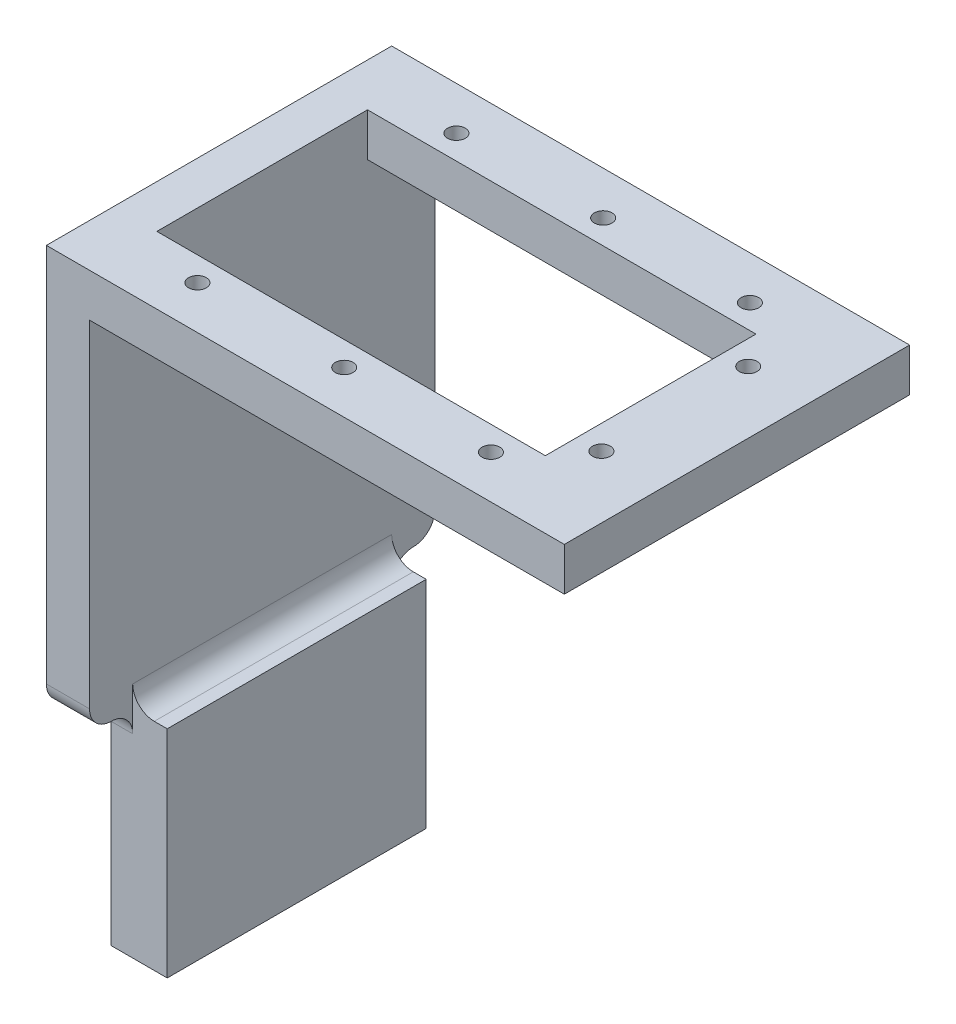
SolidWorks part; units mm, degrees
material "ABS"
ref_plane "Front Plane" through (0, 0, 0) normal (0, 0, 1) x (1, 0, 0)
ref_plane "Top Plane" through (0, 0, 0) normal (0, 1, 0) x (1, 0, 0)
ref_plane "Right Plane" through (0, 0, 0) normal (1, 0, 0) x (0, 0, -1)
sketch "Sketch1" plane through (0, 0, 0) normal (0, 1, 0) x (1, 0, 0)
  line L1 (0, 0) -> (60, 0)
  line L2 (0, 0) -> (0, 40)
  line L3 (0, 40) -> (60, 40)
  line L4 (60, 0) -> (60, 40)
  line L5 (5, 7.8) -> (50, 7.8)
  line L6 (5, 7.8) -> (5, 32.2)
  line L7 (5, 32.2) -> (50, 32.2)
  line L8 (50, 7.8) -> (50, 32.2)
  point P9 (5, 20)
  point P10 (0, 20)
  dimension "D1" = 40
  dimension "D2" = 60
  dimension "D3" = 45
  dimension "D4" = 24.4
  dimension "D5" = 5
extrude "Boss-Extrude1" add sketch "Sketch1" along normal blind 5
sketch "Sketch6" plane through (0, 0, 0) normal (0, -1, 0) x (1, 0, 0)
  line L0 (0, -40) -> (0, 0) construction
  line L1 (0, -40) -> (5, -40)
  line L2 (0, -40) -> (0, 0)
  line L3 (0, 0) -> (5, 0)
  line L4 (5, -40) -> (5, 0)
  line L5 (0, 0) -> (60, 0) construction
  line L6 (5, -32.2) -> (5, -7.8) construction
  line L7 (60, -40) -> (0, -40) construction
extrude "Boss-Extrude4" add sketch "Sketch6" along normal blind 41.5
sketch "Sketch7" plane through (0, -41.5, 0) normal (0, -1, 0) x (-1, 0, 0)
  line L0 (-5, 0) -> (0, 0) construction
  line L1 (-2.5, 35) -> (-9, 35)
  line L2 (-2.5, 35) -> (-2.5, 5)
  line L3 (-2.5, 5) -> (-9, 5)
  line L4 (-9, 35) -> (-9, 5)
  line L5 (-5, 40) -> (-5, 0) construction
  line L6 (-2.5, 40) -> (-2.5, 0) construction
  line L7 (0, 40) -> (-5, 40) construction
  line L8 (0, 0) -> (0, 40) construction
  point P7 (-2.5, 0)
  point P10 (-2.5, 20)
  point P17 (0, 20)
  dimension "D1" = 4
  dimension "D2" = 30
extrude "Boss-Extrude5" add sketch "Sketch7" along normal blind 25
fillet "Fillet2" radius 2.5 2 edges at (5, -41.5, -20) (2.5, -41.5, -20)
fillet "Fillet3" radius 2.5 4 edges at (2.5, -41.5, -5) (2.5, -41.5, -35) (2.5, -41.5, 0) (2.5, -41.5, -40)
sketch "Sketch8" plane through (0, 0, 0) normal (0, -1, 0) x (-1, 0, 0)
  line L0 (-1060, 20) -> (48940, 20) construction
  line L1 (-60, 0) -> (-60, 40) construction
  circle A0 centre (-52.8, 28.5) radius 1.025
  circle A1 centre (-46.5, 35) radius 1.025
  circle A2 centre (-29.5, 35) radius 1.025
  circle A3 centre (-12.5, 35) radius 1.025
  circle A4 centre (-12.5, 35) radius 1.025 construction
  circle A5 centre (-12.5, 5) radius 1.025
  circle A6 centre (-29.5, 5) radius 1.025
  circle A7 centre (-46.5, 5) radius 1.025
  circle A8 centre (-52.8, 11.5) radius 1.025
  point P20 (-60, 20)
extrude "Cut-Extrude1" cut sketch "Sketch8" against normal up to next
